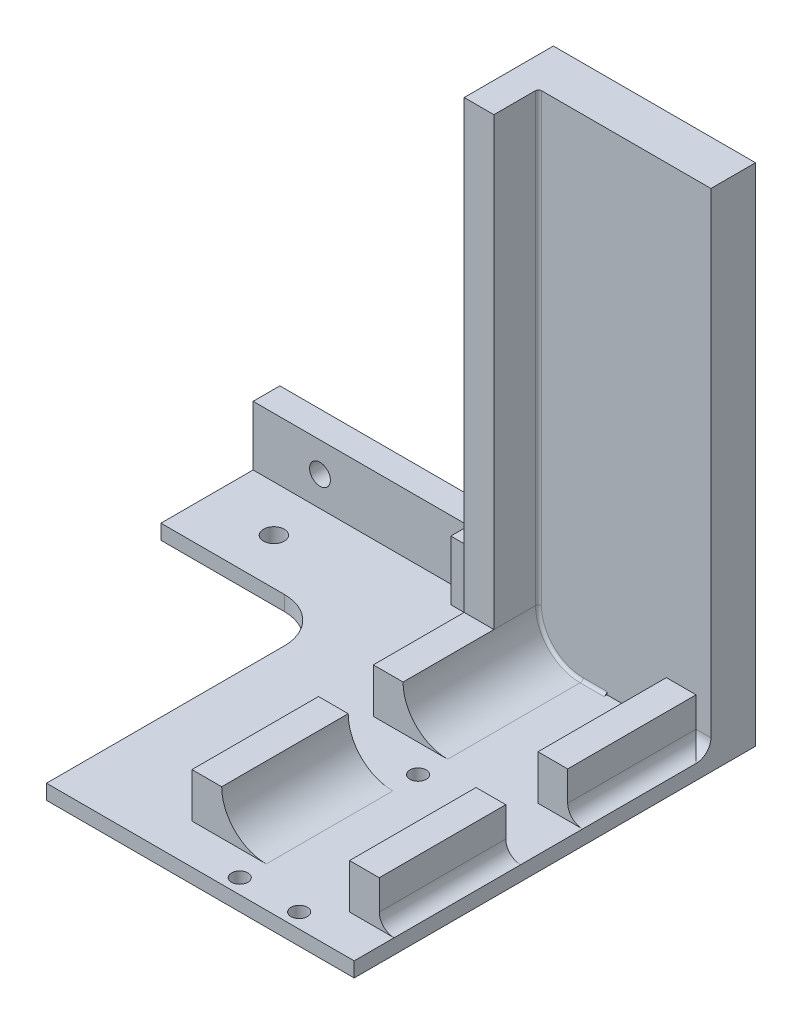
SolidWorks part; units mm, degrees
ref_plane "Front Plane" through (0, 0, 0) normal (0, 0, 1) x (1, 0, 0)
ref_plane "Top Plane" through (0, 0, 0) normal (0, 1, 0) x (1, 0, 0)
ref_plane "Right Plane" through (0, 0, 0) normal (1, 0, 0) x (0, 0, -1)
sketch "profile" plane through (0, 0, 0) normal (0, 0, 1) x (1, 0, 0)
  line L0 (11.8803, 7.4874) -> (14.5, 7.4874)
  line L1 (-5.5, 6.9749) -> (-7.8749, 4.6)
  line L2 (-7.8749, 4.6) -> (-12.1251, 4.6)
  line L3 (-12.1251, 4.6) -> (-14.5, 6.9749)
  line L4 (-8.1197, 7.4874) -> (-5.5, 7.4874)
  line L5 (-14.5, 6.9749) -> (-15.0126, 7.4874)
  line L6 (14.5, 6.9749) -> (12.1251, 4.6)
  line L7 (12.1251, 4.6) -> (7.8749, 4.6)
  line L8 (7.8749, 4.6) -> (5.5, 6.9749)
  line L9 (-14.7464, 10.3536) -> (-5.2536, 10.3536)
  line L10 (-14.5, 7.4874) -> (-11.8803, 7.4874)
  line L11 (5.5, 7.4874) -> (8.5334, 7.4874)
  line L12 (5.6673, 10.3536) -> (14.7464, 10.3536)
  line L13 (-15.0126, 7.4874) -> (-14.5, 7.4874)
  line L14 (-5.5, 6.9749) -> (-4.9874, 7.4874)
  line L15 (-4.9874, 7.4874) -> (-5.5, 7.4874)
  line L16 (5.5, 6.9749) -> (4.9874, 7.4874)
  line L17 (4.9874, 7.4874) -> (5.5, 7.4874)
  line L18 (14.5, 6.9749) -> (15.0126, 7.4874)
  line L19 (15.0126, 7.4874) -> (14.5, 7.4874)
  line L20 (-12.7464, 8.3536) -> (-14.7464, 10.3536)
  line L21 (-5.2536, 10.3536) -> (-7.2536, 8.3536)
  line L22 (7.6673, 8.3536) -> (5.6673, 10.3536)
  line L23 (14.7464, 10.3536) -> (12.7464, 8.3536)
  line L24 (-12.7464, 8.3536) -> (-11.8803, 7.4874)
  line L25 (-7.2536, 8.3536) -> (-8.1197, 7.4874)
  line L26 (7.6673, 8.3536) -> (8.5334, 7.4874)
  line L27 (12.7464, 8.3536) -> (11.8803, 7.4874)
  line L28 (-14.7464, 10.3536) -> (-20, 10.3536)
  line L29 (-20, 10.3536) -> (-20, 15.3536)
  line L30 (-20, 15.3536) -> (20, 15.3536)
  line L31 (20, 15.3536) -> (20, 10.3536)
  line L32 (20, 10.3536) -> (14.7464, 10.3536)
  line L33 (-5.2536, 10.3536) -> (5.6673, 10.3536)
  point P0 (-10, 4.6)
  point P1 (10, 4.6)
  dimension "D1" = 4.2503
  dimension "D2" = 5.7536
  dimension "D3" = 15.7497
  dimension "D4" = 20
  dimension "D5" = 5
extrude "Boss-Extrude1" add sketch "profile" along normal blind 250 contours L9 L33 L12 L32 L31 L30 L29 L28 region at (0, 12.8536, 0)
extrude "Boss-Extrude2" add sketch "Sketch1<3>" along normal blind 50 separate body contours L25 L21 L9 L20 L24 L10 L13 L5 L3 L2 L1 L14 L15 L4 | L27 L23 L12 L22 L26 L11 L17 L16 L8 L7 L6 L18 L19 L0 region at (10.0959, 7.5838, 0) region at (-10, 7.6238, 0)
sketch "Sketch1<3>" plane through (0, 0, 0) normal (0, 0, 1) x (1, 0, 0) same geometry as "profile"
pattern_linear "LPattern1" count 4 spacing 60 along (0, 0, 1) of "Boss-Extrude2"
sketch "Sketch2" plane through (0, 10.3536, 0) normal (0, -1, 0) x (1, 0, 0)
  line L0 (10, 250) -> (10, 0) construction
  line L1 (-20, 250) -> (20, 250) construction
  line L2 (12.1251, 0) -> (7.8749, 0) construction
  line L3 (-10, 230) -> (-10, 0) construction
  line L4 (-7.8749, 230) -> (-12.1251, 230) construction
  line L5 (-7.8749, 0) -> (-12.1251, 0) construction
  line L6 (-7.8749, 180) -> (-7.8749, 170) construction
  line L7 (-7.8749, 180) -> (-12.1251, 180) construction
  circle A0 centre (-10, 175) radius 2.75
  circle A1 centre (10, 175) radius 2.75
  circle A2 centre (-10, 115) radius 2.75
  circle A3 centre (10, 115) radius 2.75
  circle A4 centre (-10, 55) radius 2.75
  circle A5 centre (10, 55) radius 2.75
  point P21 (-7.8749, 175)
  dimension "D1" = 5.5
  dimension "D2" = 3
extrude "Cut-Extrude1" cut sketch "Sketch2" against normal through all
sketch "upper_acrylic_supp" plane through (0, 15.3536, 0) normal (0, 1, 0) x (1, 0, 0)
  line L0 (-20, 0) -> (20, 0) construction
  line L1 (-20, -250) -> (-34.5, -250) construction
  line L2 (-20, -250) -> (-20, 0) construction
  line L3 (-20, 0) -> (-34.5, 0) construction
  line L4 (-34.5, -250) -> (-34.5, 0) construction
  line L6 (-34.5, -250) -> (-24.5, -250)
  line L7 (-34.5, -250) -> (-34.5, -183.9264)
  line L8 (-34.5, -183.9264) -> (-24.5, -183.9264)
  line L9 (-24.5, -250) -> (-24.5, -183.9264)
  line L10 (-34.5, -165.3527) -> (-24.5, -165.3527)
  line L11 (-34.5, -165.3527) -> (-34.5, -123.8775)
  line L12 (-34.5, -123.8775) -> (-24.5, -123.8775)
  line L13 (-24.5, -165.3527) -> (-24.5, -123.8775)
  line L14 (-34.5, -106.5661) -> (-24.5, -106.5661)
  line L15 (-34.5, -106.5661) -> (-34.5, -64.0089)
  line L16 (-34.5, -64.0089) -> (-24.5, -64.0089)
  line L17 (-24.5, -106.5661) -> (-24.5, -64.0089)
  line L18 (-34.5, -45.5583) -> (-24.5, -45.5583)
  line L19 (-34.5, -45.5583) -> (-34.5, 0)
  line L20 (-34.5, 0) -> (-24.5, 0)
  line L21 (-24.5, -45.5583) -> (-24.5, 0)
  line L22 (-20, -250) -> (-40, -250)
  line L23 (-20, -250) -> (-20, 0)
  line L24 (-20, 0) -> (-40, 0)
  line L25 (-40, -250) -> (-40, 0)
  line M21 (-20, 0) -> (-20, -250)
  dimension "D1" = 5.5
  dimension "D2" = 10
  dimension "D3" = 20
extrude "Boss-Extrude3" add sketch "upper_acrylic_supp" against normal blind 5 contours L25 L22 L24 L21 L18 L19 L17 L14 L15 L16 L13 L10 L11 L12 L9 L6 L7 L8 M21 | L14 L17 L16 L15 | L10 L13 L12 L11 | L6 L9 L8 L7 | L18 L21 L20 L19 region at (-29.5, 15.3536, 216.9632) region at (-30.3215, 15.3536, 123.2164) region at (-29.5, 15.3536, 22.7792) region at (-29.5, 15.3536, 144.6151) region at (-29.5, 15.3536, 85.2875)
extrude "Boss-Extrude4" add sketch "upper_acrylic_supp<3>" along normal blind 15 contours L6 L9 L8 L7 | L10 L13 L12 L11 | L14 L17 L16 L15 | L18 L21 L20 L19 region at (-29.5, 15.3536, 216.9632) region at (-29.5, 15.3536, 22.7792) region at (-29.5, 15.3536, 144.6151) region at (-29.5, 15.3536, 85.2875)
sketch "upper_acrylic_supp<3>" plane through (0, 15.3536, 0) normal (0, 1, 0) x (1, 0, 0) same geometry as "upper_acrylic_supp"
fillet "Fillet1" radius 15 4 edges at (-24.5, 15.3536, 22.7792) (-24.5, 15.3536, 85.2875) (-24.5, 15.3536, 144.6151) (-24.5, 15.3536, 216.9632)
sketch "Sketch4" plane through (0, 15.3536, 0) normal (0, 1, 0) x (1, 0, 0)
  line L0 (20, -250) -> (20, 0) construction
  line L1 (-40, -250) -> (20, -250)
  line L2 (-40, -250) -> (-40, -265)
  line L3 (-40, -265) -> (20, -265)
  line L4 (20, -250) -> (20, -265)
  line L5 (-40, 0) -> (20, 0)
  line L6 (-40, 0) -> (-40, 15)
  line L7 (-40, 15) -> (20, 15)
  line L8 (20, 0) -> (20, 15)
  line L10 (-34.5, -265) -> (-34.5, 15) construction
  dimension "D1" = 15
  dimension "D2" = 15
extrude "Boss-Extrude5" add sketch "Sketch4" along normal mid plane 10
extrude "Boss-Extrude6" add sketch "Sketch4<3>" along normal blind 60
sketch "Sketch4<3>" plane through (0, 15.3536, 0) normal (0, 1, 0) x (1, 0, 0) same geometry as "Sketch4"
sketch "Sketch5" plane through (0, 0, 250) normal (0, 0, -1) x (-1, 0, 0)
  line L0 (-20, 75.3536) -> (40, 75.3536) construction
  line L1 (40, 15.3536) -> (34.5, 15.3536)
  line L2 (40, 15.3536) -> (40, 75.3536)
  line L3 (40, 75.3536) -> (34.5, 75.3536)
  line L4 (34.5, 15.3536) -> (34.5, 75.3536)
  line L6 (34.5, 15.3536) -> (24.5, 15.3536)
  line L7 (34.5, 15.3536) -> (34.5, 75.3536)
  line L8 (34.5, 75.3536) -> (24.5, 75.3536)
  line L9 (24.5, 15.3536) -> (24.5, 75.3536)
  line M5 (40, 75.3536) -> (-20, 75.3536)
  line M9 (24.5, 30.3536) -> (34.5, 30.3536)
  dimension "D1" = 5.5
  dimension "D2" = 10
extrude "Boss-Extrude7" add sketch "Sketch5" along normal blind 15 contours L9 L4 M9 M5 region at (-29.5, 52.8536, 250)
extrude "Boss-Extrude8" add sketch "Sketch5<3>" against normal blind 15 from surface contours L9 L4 M9 M5 region at (-29.5, 52.8536, 250) starting at face at (-18.2633, 33.7152, 0)
sketch "Sketch5<3>" plane through (0, 0, 250) normal (0, 0, -1) x (-1, 0, 0) same geometry as "Sketch5"
fillet "Fillet2" radius 1 6 edges at (5.25, 15.3536, 0) (-20.1066, 19.747, 0) (5.25, 15.3536, 250) (-20.1066, 19.747, 250) (-24.5, 52.8536, 0) (-24.5, 52.8536, 250)
sketch "Sketch6" plane through (-40, 0, 0) normal (-1, 0, 0) x (0, 0, 1)
  line L1 (250, 15.3536) -> (256, 15.3536)
  line L2 (250, 15.3536) -> (250, 75.3536)
  line L3 (250, 75.3536) -> (256, 75.3536)
  line L4 (256, 15.3536) -> (256, 75.3536)
  line L6 (0, 15.3536) -> (-6, 15.3536)
  line L7 (0, 15.3536) -> (0, 75.3536)
  line L8 (0, 75.3536) -> (-6, 75.3536)
  line L9 (-6, 15.3536) -> (-6, 75.3536)
  dimension "D1" = 6
  dimension "D2" = 6
extrude "Cut-Extrude2" cut sketch "Sketch6" against normal blind 6
sketch "Sketch7" plane through (-40, 0, 0) normal (-1, 0, 0) x (0, 0, 1)
  line L8 (265, 75.3536) -> (256, 75.3536)
  line L9 (256, 75.3536) -> (256, 15.3536)
  line L10 (256, 15.3536) -> (-6, 15.3536)
  line L11 (-6, 15.3536) -> (-6, 75.3536)
  line L12 (-6, 75.3536) -> (-15, 75.3536)
  line L13 (-15, 75.3536) -> (-15, 10.3536)
  line L14 (-15, 10.3536) -> (265, 10.3536)
  line L15 (265, 10.3536) -> (265, 75.3536)
  line L16 (265, 75.3536) -> (256, 75.3536)
  line L17 (256, 75.3536) -> (256, 15.3536)
  line L18 (256, 15.3536) -> (-6, 15.3536)
  line L19 (-6, 15.3536) -> (-6, 75.3536)
  line L20 (-6, 75.3536) -> (-15, 75.3536)
  line L21 (-15, 75.3536) -> (-15, 10.3536)
  line L22 (-15, 10.3536) -> (265, 10.3536)
  line L23 (265, 10.3536) -> (265, 75.3536)
  dimension "D1" = 0
extrude "Boss-Extrude9" add sketch "Sketch7" along normal blind 30
sketch "Sketch8" plane through (-70, 0, 0) normal (-1, 0, 0) x (0, 0, 1)
  line L0 (-15, 10.3536) -> (265, 10.3536) construction
  line L1 (-44.3745, 35.3536) -> (289.2282, 35.3536)
  line L2 (-44.3745, 35.3536) -> (-44.3745, 94.3849)
  line L3 (-44.3745, 94.3849) -> (289.2282, 94.3849)
  line L4 (289.2282, 35.3536) -> (289.2282, 94.3849)
  dimension "D1" = 25
extrude "Cut-Extrude3" cut sketch "Sketch8" against normal blind 150
sketch "Sketch9" plane through (-34, 0, 0) normal (-1, 0, 0) x (0, 0, 1)
  line L4 (256, 15.3536) -> (256, 35.3536)
  line L5 (256, 35.3536) -> (250, 35.3536)
  line L6 (250, 35.3536) -> (250, 15.3536)
  line L7 (250, 15.3536) -> (256, 15.3536)
  line L8 (256, 15.3536) -> (256, 35.3536)
  line L9 (256, 35.3536) -> (250, 35.3536)
  line L10 (250, 35.3536) -> (250, 15.3536)
  line L11 (250, 15.3536) -> (256, 15.3536)
  line L12 (0, 35.3536) -> (-6, 35.3536)
  line L13 (-6, 35.3536) -> (-6, 15.3536)
  line L14 (-6, 15.3536) -> (0, 15.3536)
  line L15 (0, 15.3536) -> (0, 35.3536)
  line L16 (0, 35.3536) -> (-6, 35.3536)
  line L17 (-6, 35.3536) -> (-6, 15.3536)
  line L18 (-6, 15.3536) -> (0, 15.3536)
  line L19 (0, 15.3536) -> (0, 35.3536)
  dimension "D1" = 0
  dimension "D2" = 0
extrude "cloth_escape_gap" add sketch "Sketch9" along normal blind 20
sketch "Sketch11" plane through (-70, 0, 0) normal (-1, 0, 0) x (0, 0, 1)
  line L0 (256, 35.3536) -> (256, 15.3536) construction
  line L1 (-15, 35.3536) -> (-6, 35.3536)
  line L2 (-15, 35.3536) -> (-15, 15.3536)
  line L3 (-15, 15.3536) -> (-6, 15.3536)
  line L4 (-6, 35.3536) -> (-6, 15.3536)
  line L5 (265, 35.3536) -> (256, 35.3536)
  line L6 (265, 35.3536) -> (265, 15.3536)
  line L7 (265, 15.3536) -> (256, 15.3536)
  line L8 (256, 35.3536) -> (256, 15.3536)
  line L9 (256, 15.3536) -> (256, 35.3536) construction
extrude "Boss-Extrude11" add sketch "Sketch11" along normal blind 100
sketch "Sketch12" plane through (0, 10.3536, 0) normal (0, -1, 0) x (1, 0, 0)
  line L0 (-70, -15) -> (-170, -10.5)
  line L1 (-170, -15) -> (-170, -6) construction
  line L2 (-170, -10.5) -> (-170, -15)
  line L3 (-170, -15) -> (-70, -15) construction
  line L4 (-170, -15) -> (-70, -15)
  line L5 (-70, 265) -> (-170, 260.5)
  line L6 (-170, 256) -> (-170, 265) construction
  line L7 (-170, 260.5) -> (-170, 265)
  line L8 (-170, 265) -> (-70, 265)
extrude "Cut-Extrude4" cut sketch "Sketch12" against normal blind 68 contours L8 L7 L5 | L0 L2 L4 region at (-136.6667, 10.3536, 263.5)
sketch "Sketch13" plane through (-70, 0, 0) normal (-1, 0, 0) x (0, 0, 1)
  line L0 (256, 15.3536) -> (265, 15.3536) construction
  line L1 (-15, 10.3536) -> (25, 10.3536)
  line L2 (-15, 10.3536) -> (-15, 15.3536)
  line L3 (-15, 15.3536) -> (25, 15.3536)
  line L4 (25, 10.3536) -> (25, 15.3536)
  line L5 (265, 10.3536) -> (225, 10.3536)
  line L6 (265, 10.3536) -> (265, 15.3536)
  line L7 (265, 15.3536) -> (225, 15.3536)
  line L8 (225, 10.3536) -> (225, 15.3536)
  line L9 (256, 15.3536) -> (-6, 15.3536) construction
  dimension "D1" = 40
  dimension "D2" = 40
extrude "Boss-Extrude13" add sketch "Sketch13" along normal blind 100
sketch "Sketch14" plane through (0, 15.3536, 0) normal (0, 1, 0) x (1, 0, 0)
  line L3 (-70, -265) -> (-170, -260.5)
  line L4 (-170, -260.5) -> (-170, -265)
  line L5 (-170, -265) -> (-70, -265)
  line L6 (-70, -265) -> (-170, -260.5)
  line L7 (-170, -260.5) -> (-170, -265)
  line L8 (-170, -265) -> (-70, -265)
  line L9 (-170, 15) -> (-170, 10.5)
  line L10 (-170, 10.5) -> (-70, 15)
  line L11 (-70, 15) -> (-170, 15)
  line L12 (-170, 15) -> (-170, 10.5)
  line L13 (-170, 10.5) -> (-70, 15)
  line L14 (-70, 15) -> (-170, 15)
  dimension "D1" = 0
  dimension "D2" = 0
extrude "Cut-Extrude5" cut sketch "Sketch14" against normal blind 100
fillet "Fillet3" radius 15 2 edges at (-70, 12.8536, 25) (-70, 12.8536, 225)
sketch "Sketch16" plane through (0, 15.3536, 0) normal (0, 1, 0) x (1, 0, 0)
  line L0 (20, -1) -> (-9.5, -1) construction
  line L1 (-34.5, -235) -> (18.5, -235) construction
  line L2 (-34.5, -235) -> (-34.5, -1) construction
  line L3 (-34.5, -1) -> (18.5, -1) construction
  line L4 (18.5, -235) -> (18.5, -1) construction
  line L5 (20, -265) -> (-70, -265) construction
  line L6 (18.5, -265) -> (33.5, -265)
  line L7 (18.5, -265) -> (18.5, 15)
  line L8 (18.5, 15) -> (33.5, 15)
  line L9 (33.5, -265) -> (33.5, 15)
  line L10 (-70, 15) -> (20, 15) construction
  line L11 (18.5, -250) -> (33.5, -250)
  line L12 (18.5, 0) -> (33.5, 0)
  line L13 (-23.5, -250) -> (20, -250) construction
  line L14 (-9.5, 0) -> (20, 0) construction
  line L15 (18.5, -250) -> (28.5, -250)
  line L16 (28.5, -250) -> (28.5, -183.9264)
  line L17 (28.5, 0) -> (18.5, 0)
  line L18 (18.5, -183.9264) -> (28.5, -183.9264)
  line L19 (18.5, -165.3527) -> (28.5, -165.3527)
  line L20 (18.5, -123.8775) -> (28.5, -123.8775)
  line L21 (18.5, -106.5661) -> (28.5, -106.5661)
  line L22 (18.5, -64.0089) -> (28.5, -64.0089)
  line L23 (18.5, -43.1778) -> (28.5, -43.1778)
  line L24 (-34.5, -165.3527) -> (-9.5, -165.3527) construction
  line L25 (-34.5, -183.9264) -> (-9.5, -183.9264) construction
  line L26 (-34.5, -106.5661) -> (-9.5, -106.5661) construction
  line L27 (-34.5, -123.8775) -> (-9.5, -123.8775) construction
  line L28 (-9.5, -64.0089) -> (-24.5, -64.0089) construction
  line L30 (28.5, -165.3527) -> (28.5, -123.8775)
  line L31 (28.5, -106.5661) -> (28.5, -64.0089)
  line L32 (28.5, -43.1778) -> (28.5, 0)
  line M38 (-9.5, -249) -> (20, -249)
  line M39 (20, -249) -> (20, -1)
  line M40 (20, -1) -> (-9.5, -1)
  dimension "D1" = 53
  dimension "D2" = 15
  dimension "D3" = 10
extrude "Boss-Extrude14" add sketch "Sketch16" along direction (0, -1, 0) on the side of the normal up to surface (20 mm away) from surface contours L7 L12 L9 L8 | L11 L7 L6 L9 region at (26, 15.3536, 257.5) region at (26, 15.3536, -7.5) up to face at (-51.6423, 35.3536, 251.8089) starting at face at (-10, 10.3536, 25)
extrude "Cut-Extrude6" cut sketch "Sketch16<5>" against normal blind 10 and the other way blind 30 contours L11 L7 L6 L9 | L32 L23 L22 L31 L21 L20 L30 L19 L18 L16 L11 L9 L12 M39 | L19 L30 L20 M39 | L21 L31 L22 M39 | L23 L32 L12 L7 M40 M39 | L7 L12 L9 L8 | L7 L23 M39 M40 | L23 L7 L22 M39 | L22 L7 L21 M39 | L21 L7 L20 M39 | L20 L7 L19 M39 | L19 L7 L18 M39 | L18 L7 M38 M39 | L18 L7 L11 L16 M39 M38 region at (26, 15.3536, 257.5) region at (24.2367, 15.3536, 217.0499) region at (29.1213, 15.3536, 121.3942) region at (19.25, 15.3536, 216.4632) region at (26, 15.3536, -7.5) region at (19.25, 15.3536, 174.6396) region at (24.2296, 15.3536, 21.5031) region at (19.25, 15.3536, 144.6151) region at (19.25, 15.3536, 115.2218) region at (24.25, 15.3536, 144.6151) region at (19.25, 15.3536, 22.0889) region at (19.25, 15.3536, 53.5934) region at (19.25, 15.3536, 85.2875) region at (24.25, 15.3536, 85.2875)
sketch "Sketch16<5>" plane through (0, 15.3536, 0) normal (0, 1, 0) x (1, 0, 0) same geometry as "Sketch16"
extrude "Boss-Extrude15" add sketch "Sketch16<6>" against normal up to surface (5 mm away) contours L32 L23 L22 L31 L21 L20 L30 L19 L18 L16 L11 L9 L12 M39 | L18 L7 L11 L16 M39 M38 | L11 L7 L6 L9 | L19 L30 L20 M39 | L21 L31 L22 M39 | L23 L32 L12 L7 M40 M39 | L7 L12 L9 L8 | L7 L23 M39 M40 | L23 L7 L22 M39 | L22 L7 L21 M39 | L21 L7 L20 M39 | L20 L7 L19 M39 | L19 L7 L18 M39 | L18 L7 M38 M39 region at (26, 15.3536, 257.5) region at (24.2367, 15.3536, 217.0499) region at (29.1213, 15.3536, 121.3942) region at (19.25, 15.3536, 216.4632) region at (26, 15.3536, -7.5) region at (19.25, 15.3536, 174.6396) region at (24.2296, 15.3536, 21.5031) region at (19.25, 15.3536, 144.6151) region at (19.25, 15.3536, 115.2218) region at (24.25, 15.3536, 144.6151) region at (19.25, 15.3536, 22.0889) region at (19.25, 15.3536, 53.5934) region at (19.25, 15.3536, 85.2875) region at (24.25, 15.3536, 85.2875) up to face at (-90.5656, 10.3536, 125)
sketch "Sketch16<6>" plane through (0, 15.3536, 0) normal (0, 1, 0) x (1, 0, 0) same geometry as "Sketch16"
extrude "Boss-Extrude16" add sketch "Sketch16<7>" along normal up to surface (20 mm away) contours L11 L7 L6 L9 | L7 L12 L9 L8 region at (26, 15.3536, 257.5) region at (26, 15.3536, -7.5) up to face at (-51.8923, 35.3536, 251.8089)
sketch "Sketch16<7>" plane through (0, 15.3536, 0) normal (0, 1, 0) x (1, 0, 0) same geometry as "Sketch16"
extrude "Boss-Extrude17" add sketch "Sketch16<8>" along normal up to surface (15 mm away) contours L18 L7 L11 L16 M39 M38 | L19 L30 L20 M39 | L21 L31 L22 M39 | L23 L32 L12 L7 M40 M39 | L7 L23 M39 M40 | L22 L7 L21 M39 | L20 L7 L19 M39 | L18 L7 M38 M39 region at (24.2367, 15.3536, 217.0499) region at (19.25, 15.3536, 216.4632) region at (24.2296, 15.3536, 21.5031) region at (19.25, 15.3536, 144.6151) region at (24.25, 15.3536, 144.6151) region at (19.25, 15.3536, 22.0889) region at (19.25, 15.3536, 85.2875) region at (24.25, 15.3536, 85.2875) up to face at (-29.5, 30.3536, 209.4632)
sketch "Sketch16<8>" plane through (0, 15.3536, 0) normal (0, 1, 0) x (1, 0, 0) same geometry as "Sketch16"
extrude "Boss-Extrude18" add sketch "Sketch14<2>" along normal up to surface (20 mm away) and the other way up to surface (5 mm away) up to face at (-49.3923, 35.3536, -1.8089) other way up to face at (-88.0656, 10.3536, 125)
sketch "Sketch14<2>" plane through (0, 15.3536, 0) normal (0, 1, 0) x (1, 0, 0) same geometry as "Sketch14"
fillet "Fillet4" radius 5 6 edges at (31, 15.3536, 250) (31, 15.3536, 0) (28.5, 15.3536, 21.5889) (28.5, 15.3536, 85.2875) (28.5, 15.3536, 144.6151) (28.5, 15.3536, 216.9632)
sketch "Sketch18" plane through (0, 35.3536, 0) normal (0, 1, 0) x (1, 0, 0)
  line L2 (-34.5, -250) -> (-34.5, -265)
  line L3 (-34.5, 15) -> (-34.5, 0)
  line L12 (-23.5, 0) -> (33.5, 0)
  line L13 (33.5, 0) -> (33.5, 15)
  line L14 (33.5, 15) -> (-170, 15)
  line L15 (-170, 15) -> (-170, 6)
  line L30 (-170, 6) -> (-54, 6)
  line L32 (-54, 6) -> (-54, 0)
  line L38 (-54, 0) -> (-34.5, 0)
  line L39 (-34.5, 0) -> (-34.5, -15)
  line L50 (-34.5, -15) -> (-24.5, -15)
  line L51 (-24.5, -15) -> (-24.5, -1)
  line L52 (-23.5, 0) -> (33.5, 0)
  line L53 (33.5, 0) -> (33.5, 15)
  line L54 (33.5, 15) -> (-34.5, 15)
  line L59 (-34.5, 0) -> (-34.5, -15)
  line L60 (-34.5, -15) -> (-24.5, -15)
  line L61 (-24.5, -15) -> (-24.5, -1)
  line L62 (-170, -265) -> (33.5, -265)
  line L63 (33.5, -265) -> (33.5, -250)
  line L64 (33.5, -250) -> (-23.5, -250)
  line L65 (-24.5, -249) -> (-24.5, -235)
  line L66 (-24.5, -235) -> (-34.5, -235)
  line L67 (-34.5, -235) -> (-34.5, -250)
  line L68 (-34.5, -250) -> (-54, -250)
  line L69 (-54, -250) -> (-54, -256)
  line L70 (-54, -256) -> (-170, -256)
  line L71 (-170, -256) -> (-170, -265)
  line L72 (-34.5, -265) -> (33.5, -265)
  line L73 (33.5, -265) -> (33.5, -250)
  line L74 (33.5, -250) -> (-23.5, -250)
  line L75 (-24.5, -249) -> (-24.5, -235)
  line L76 (-24.5, -235) -> (-34.5, -235)
  line L77 (-34.5, -235) -> (-34.5, -250)
  arc A5 (-23.5, 0) -> (-24.5, -1) centre (-23.5, -1) ccw
  arc A6 (-23.5, 0) -> (-24.5, -1) centre (-23.5, -1) ccw
  arc A7 (-24.5, -249) -> (-23.5, -250) centre (-23.5, -249) ccw
  arc A8 (-24.5, -249) -> (-23.5, -250) centre (-23.5, -249) ccw
  dimension "D1" = 0
  dimension "D2" = 0
extrude "Boss-Extrude21" add sketch "Sketch18" along normal blind 170 from surface starting at face at (-91.6787, 10.3536, 125)
sketch "Sketch19" plane through (0, 15.3536, 0) normal (0, 1, 0) x (1, 0, 0)
  line L0 (-170, -25) -> (-170, 6) construction
  line L1 (-70, -125) -> (-196.5165, -125) construction
  line L2 (-70, -210) -> (-70, -40) construction
  circle A0 centre (-154, -9.5) radius 3.5
  circle A1 centre (-104, -9.5) radius 3.5
  circle A2 centre (-104, -240.5) radius 3.5
  circle A3 centre (-154, -240.5) radius 3.5
  point P6 (-170, -9.5)
  dimension "D1" = 7
  dimension "D2" = 50
  dimension "D3" = 50
extrude "Cut-Extrude7" cut sketch "Sketch19" against normal blind 10
sketch "Sketch20" plane through (0, 0, 256) normal (0, 0, -1) x (-1, 0, 0)
  line L4 (34.5, 35.3536) -> (34.5, 15.3536)
  line L5 (34.5, 15.3536) -> (54, 15.3536)
  line L6 (54, 15.3536) -> (54, 35.3536)
  line L7 (54, 35.3536) -> (34.5, 35.3536)
  line L8 (34.5, 35.3536) -> (34.5, 15.3536)
  line L9 (34.5, 15.3536) -> (54, 15.3536)
  line L10 (54, 15.3536) -> (54, 35.3536)
  line L11 (54, 35.3536) -> (34.5, 35.3536)
  circle A0 centre (104, 25.3536) radius 3.5
  circle A1 centre (154, 25.3536) radius 3.5
  point P8 (54, 25.3536)
  dimension "D3" = 7
  dimension "D2" = 50
  dimension "D4" = 50
  dimension "D1" = 0
extrude "Cut-Extrude8" cut sketch "Sketch20" against normal blind 10 and the other way blind 355 contours A0 | A1 region at (-104, 25.3536, 256) region at (-154, 25.3536, 256)
sketch "Sketch21" plane through (0, 0, 0) normal (0, 0, 1) x (1, 0, 0)
  line L1 (13.5, 15.3536) -> (-1.5, 15.3536)
  line L2 (13.5, 15.3536) -> (13.5, 212.8546)
  line L3 (13.5, 212.8546) -> (-1.5, 212.8546)
  line L4 (-1.5, 15.3536) -> (-1.5, 212.8546)
  line L6 (18.5, 15.3536) -> (-9.5, 15.3536) construction
  line L7 (18.5, 30.3536) -> (18.5, 16.3536) construction
  dimension "D1" = 15
  dimension "D2" = 5
extrude "Cut-Extrude9" cut sketch "Sketch21" along normal blind 340
sketch "Sketch22" plane through (0, 0, 0) normal (0, 1, 0) x (1, 0, 0)
  line L0 (33.5, 15) -> (-34.5, 15) construction
  line L5 (33.5, 15) -> (-126.5, 15)
  line L6 (33.5, 15) -> (33.5, -120)
  line L7 (33.5, -120) -> (-126.5, -120)
  line L8 (-126.5, 15) -> (-126.5, -120)
  line L9 (33.5, 0) -> (33.5, 15) construction
  line L10 (33.5, -265) -> (33.5, -250) construction
  line L11 (33.5, -265) -> (-126.5, -265)
  line L12 (33.5, -265) -> (33.5, -130)
  line L13 (33.5, -130) -> (-126.5, -130)
  line L14 (-126.5, -265) -> (-126.5, -130)
  line L15 (-126.5, -120) -> (-126.5, -130)
  line L16 (33.5, -120) -> (33.5, -130)
  line L17 (-34.5, -265) -> (-170, -265) construction
  line L19 (-126.5, 15) -> (-186.5, 15)
  line L20 (-126.5, 15) -> (-126.5, -265)
  line L21 (-126.5, -265) -> (-186.5, -265)
  line L22 (-186.5, 15) -> (-186.5, -265)
  dimension "D1" = 160
  dimension "D2" = 135
  dimension "D3" = 135
  dimension "D4" = 60
extrude "Cut-Extrude10" cut sketch "Sketch22" along normal blind 217 contours L19 L22 L21 L14 L15 L8 | L14 L11 L12 L13 | L16 L7 L15 L13 region at (-156.5, 0, 125) region at (-46.5, 0, 125) region at (-46.5, 0, 197.5)
